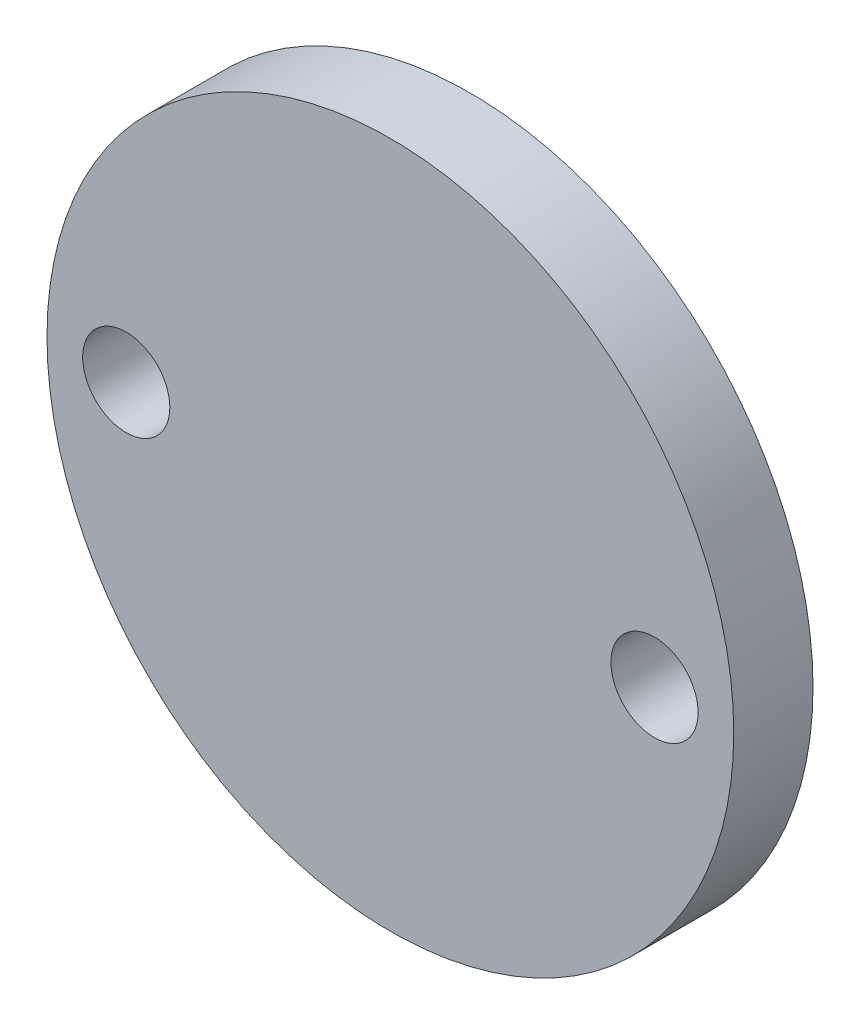
SolidWorks part; units mm, degrees
ref_plane "前视基准面" through (0, 0, 0) normal (0, 0, 1) x (1, 0, 0)
ref_plane "上视基准面" through (0, 0, 0) normal (0, 1, 0) x (1, 0, 0)
ref_plane "右视基准面" through (0, 0, 0) normal (1, 0, 0) x (0, 0, -1)
sketch "草图1" plane through (0, 0, 0) normal (0, 0, 1) x (1, 0, 0)
  line L1 (10, -988.0228) -> (10, 49011.9772) construction
  line L2 (-1000, 0) -> (49000, 0) construction
  circle A6 centre (0, 0) radius 1.65
  circle A7 centre (0, 0) radius 3
  circle A8 centre (20, 0) radius 3
  circle A9 centre (20, 0) radius 1.65
  circle A10 centre (10, 0) radius 13
  dimension "D1" = 3.3
  dimension "D2" = 6
  dimension "D3" = 10
extrude "凸台-拉伸1" add sketch "草图1" along normal blind 3 contours A8 A7 | A7 A6 | A7 A6 | A9 A8 | A9 A8 region at (0, -2.9151, 0) region at (17.0849, 0, 0) region at (10, 0, 0)
